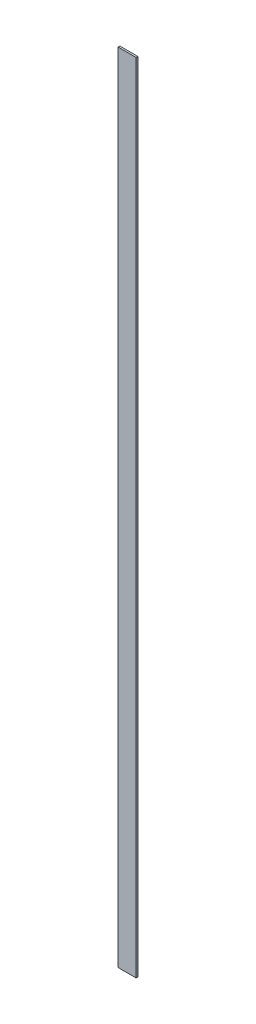
SolidWorks part; units mm, degrees
ref_plane "Спереди" through (0, 0, 0) normal (0, 0, 1) x (1, 0, 0)
ref_plane "Сверху" through (0, 0, 0) normal (0, 1, 0) x (1, 0, 0)
ref_plane "Справа" through (0, 0, 0) normal (1, 0, 0) x (0, 0, -1)
sketch "Эскиз1" plane through (0, 0, 0) normal (0, 1, 0) x (1, 0, 0)
  line L0 (0, 45) -> (0, 0)
  line L1 (0, 0) -> (45, 0)
extrude "Вытянуть-Тонкостенный1" add sketch "Эскиз1" along normal blind 2200 thin thin type one direction wall 5
sketch "Эскиз2" plane through (-5, 0, 0) normal (-1, 0, 0) x (0, 0, 1)
  line L0 (0, 0) -> (-45, 45)
  line L1 (-45, 2200) -> (-45, 0) construction
  line L2 (-45, 45) -> (-45, 0)
  line L3 (-45, 0) -> (0, 0)
  line L4 (5, 1100) -> (-53.7622, 1100) construction
  line L5 (5, 2200) -> (5, 0) construction
  line L6 (-45, 2200) -> (0, 2200)
  line L7 (-45, 2155) -> (-45, 2200)
  line L8 (0, 2200) -> (-45, 2155)
  point P9 (5, 1100)
  point P12 (-53.7622, 1100)
extrude "Вырез-Вытянуть1" cut sketch "Эскиз2" against normal through all
